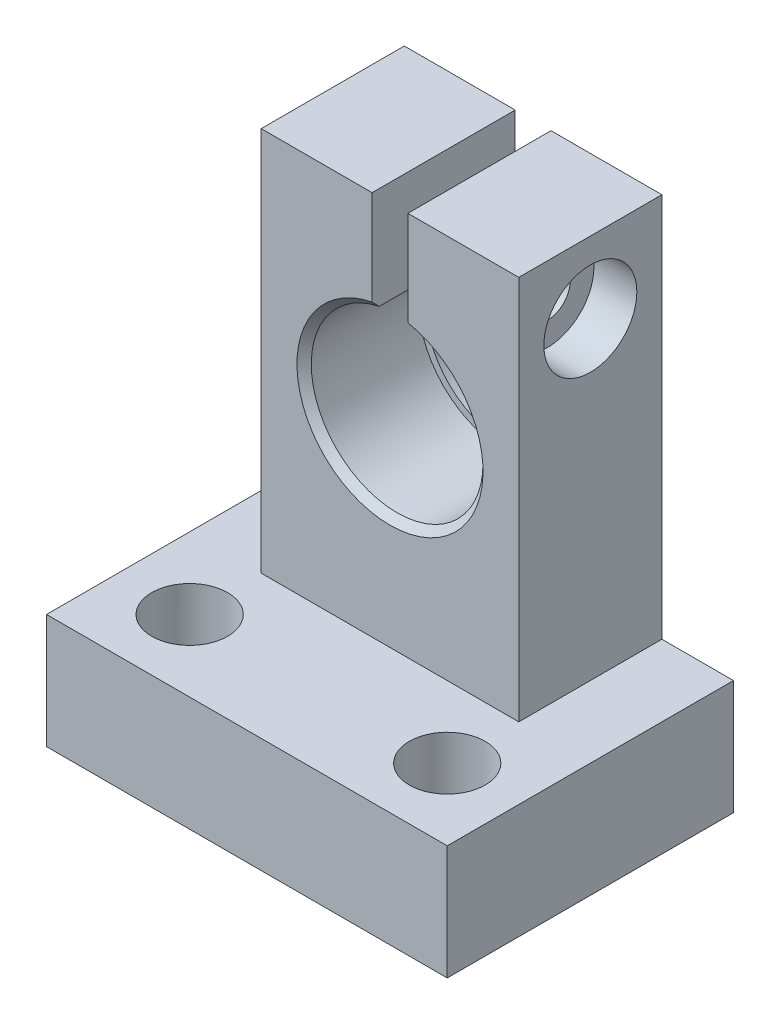
SolidWorks part; units mm, degrees
material "AISI 1045 Steel, cold drawn"
ref_plane "Front Plane" through (0, 0, 0) normal (0, 0, 1) x (1, 0, 0)
ref_plane "Top Plane" through (0, 0, 0) normal (0, 1, 0) x (1, 0, 0)
ref_plane "Right Plane" through (0, 0, 0) normal (1, 0, 0) x (0, 0, -1)
sketch "Sketch1" plane through (0, 0, 0) normal (0, 0, 1) x (1, 0, 0)
  line L1 (9, -21.9) -> (-9, -21.9)
  line L2 (9, -21.9) -> (9, 13)
  line L3 (9, 13) -> (-9, 13)
  line L4 (-9, -21.9) -> (-9, 13)
  line L5 (9, -21.9) -> (-9, 13) construction
  line L6 (9, 13) -> (-9, -21.9) construction
  circle A0 centre (0, 0) radius 6
  point P3 (0, -4.45)
  dimension "D1" = 12
  dimension "D2" = 13
  dimension "D3" = 21.9
  dimension "D4" = 18
extrude "Boss-Extrude1" add sketch "Sketch1" along normal blind 10
sketch "Sketch2" plane through (0, 0, 0) normal (0, 0, -1) x (-1, 0, 0)
  circle A0 centre (0, 0) radius 6 construction
  circle A1 centre (0, 0) radius 6
  circle A2 centre (0, 0) radius 5.5
  dimension "D1" = 0.5
extrude "Boss-Extrude2" add sketch "Sketch2" against normal blind 2
sketch "Sketch3" plane through (0, 0, 10) normal (0, 0, 1) x (1, 0, 0)
  line L0 (9, 13) -> (-9, 13) construction
  line L1 (1.25, 5.3561) -> (-1.25, 5.3561)
  line L2 (1.25, 5.3561) -> (1.25, 13)
  line L3 (1.25, 13) -> (-1.25, 13)
  line L4 (-1.25, 5.3561) -> (-1.25, 13)
  line L5 (1.25, 5.3561) -> (-1.25, 13) construction
  line L6 (1.25, 13) -> (-1.25, 5.3561) construction
  circle A0 centre (0, 0) radius 5.5 construction
  point P0 (0, 9.178)
  dimension "D1" = 2.5
extrude "Cut-Extrude1" cut sketch "Sketch3" against normal through all
hole_wizard "CBORE for M3 SHCS1" positions "Sketch4" profile "Sketch5" counterbore size "M3" standard "ANSI Metric" end condition up to next
sketch "Sketch4" plane through (9, 0, 0) normal (1, 0, 0) x (0, 0, -1)
  line L0 (0, -21.9) -> (0, 13) construction
  line L1 (-10, 13) -> (0, 13) construction
  point P0 (-5, 8)
  dimension "D1" = 5
  dimension "D2" = 5
sketch "Sketch5" plane through (9, 8, 5) normal (0, 1, 0) x (0, 0, -1)
  line L0 (0, 0) -> (0, 7.75)
  line L1 (0, 7.75) -> (1.6, 7.75)
  line L3 (1.6, 7.75) -> (1.6, 3)
  line L4 (1.6, 3) -> (3.25, 3)
  line L5 (3.25, 3) -> (3.25, 0)
  line L7 (3.25, 0) -> (0, 0)
  line L11 (0, -6.35) -> (0, 107.95) construction
  dimension "Thru Hole Dia." = 3.2
  dimension "Thru Hole Depth" = 7.75
  dimension "C'Bore Dia." = 6.5
  dimension "C'Bore Depth" = 3
hole_wizard "M3x0.5 Tapped Hole1" positions "Sketch6" profile "Sketch7" tap size "M3x0.5" standard "ANSI Metric" end condition up to next
sketch "Sketch6" plane through (-9, 0, 0) normal (-1, 0, 0) x (0, 0, 1)
  line L0 (10, 13) -> (10, -21.9) construction
  line L1 (10, 13) -> (0, 13) construction
  point P0 (5, 8)
  dimension "D1" = 5
  dimension "D2" = 5
cosmetic thread "Hole Thread1" parameters "D2"=3
sketch "Sketch7" plane through (-9, 8, 5) normal (0, 1, 0) x (0, 0, 1)
  line L0 (0, 0) -> (0, 7.75)
  line L1 (0, 7.75) -> (1.25, 7.75)
  line L2 (1.25, 7.75) -> (1.25, 0)
  line L5 (1.25, 0) -> (0, 0)
  line L11 (0, -6.35) -> (0, 107.95) construction
  dimension "Thru Tap Drill Dia." = 2.5
  dimension "Thru Tap Drill Depth" = 7.75
chamfer "Chamfer1" distance 0.5 angle 45 1 edges at (0, -6, 10)
sketch "Sketch11" plane through (-9, 0, 0) normal (-1, 0, 0) x (0, 0, 1)
  line L0 (0, 13) -> (0, -21.9) construction
  line L1 (0, -21.9) -> (10, -21.9)
  line L2 (0, -21.9) -> (0, -13.9)
  line L3 (0, -13.9) -> (10, -13.9)
  line L4 (10, -21.9) -> (10, -13.9)
  line L5 (10, 13) -> (10, -21.9) construction
  dimension "D1" = 8
extrude "Boss-Extrude4" add sketch "Sketch11" along normal blind 5
mirror "Mirror1" about plane through (0, 0, 0) normal (1, 0, 0) of "Boss-Extrude4"
sketch "Sketch8" plane through (0, -21.9, 0) normal (0, -1, 0) x (1, 0, 0)
  line L0 (-14, 0) -> (-14, 10) construction
  line L1 (-14, 10) -> (14, 10)
  line L2 (-14, 10) -> (-14, 20)
  line L3 (-14, 20) -> (14, 20)
  line L4 (14, 10) -> (14, 20)
  dimension "D1" = 10
extrude "Boss-Extrude3" add sketch "Sketch8" against normal up to surface (8 mm away) up to face at (-11.5, -13.9, 5)
hole_wizard "M5 Clearance Hole1" positions "Sketch9" profile "Sketch10" hole size "M5" standard "ANSI Metric" end condition up to next
sketch "Sketch9" plane through (0, -13.9, 0) normal (0, 1, 0) x (1, 0, 0)
  line L0 (14, -20) -> (-14, -20) construction
  line L1 (-14, -20) -> (-14, 0) construction
  line L2 (0, -10) -> (0, -20) construction
  line L4 (-9, -10) -> (9, -10) construction
  point P0 (-9, -15)
  point P14 (9, -15)
  dimension "D1" = 5
  dimension "D2" = 5
sketch "Sketch10" plane through (-9, -13.9, 15) normal (1, 0, 0) x (0, 0, 1)
  line L0 (0, 0) -> (0, 8)
  line L1 (0, 8) -> (2.65, 8)
  line L2 (2.65, 8) -> (2.65, 0)
  line L5 (2.65, 0) -> (0, 0)
  line L11 (0, -6.35) -> (0, 107.95) construction
  dimension "Thru Hole Dia." = 5.3
  dimension "Thru Hole Depth" = 8
